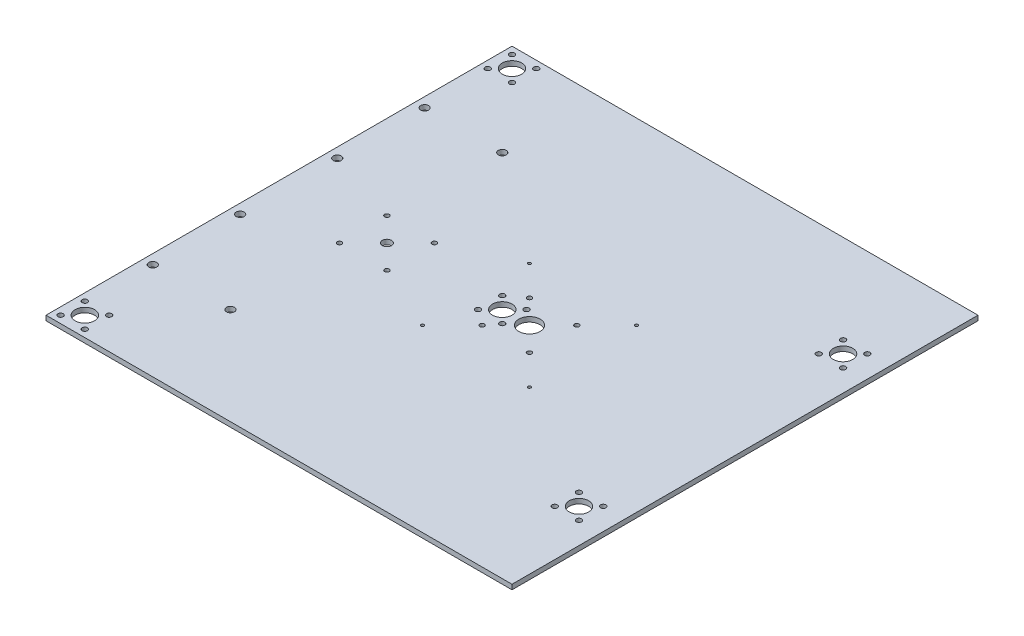
SolidWorks part; units mm, degrees
ref_plane "Front Plane" through (0, 0, 0) normal (0, 0, 1) x (1, 0, 0)
ref_plane "Top Plane" through (0, 0, 0) normal (0, 1, 0) x (1, 0, 0)
ref_plane "Right Plane" through (0, 0, 0) normal (1, 0, 0) x (0, 0, -1)
sketch "Sketch1" plane through (0, 0, 0) normal (0, 1, 0) x (1, 0, 0)
  line L1 (-152.4, -152.4) -> (152.4, -152.4)
  line L2 (-152.4, -152.4) -> (-152.4, 152.4)
  line L3 (-152.4, 152.4) -> (152.4, 152.4)
  line L4 (152.4, -152.4) -> (152.4, 152.4)
  line L5 (-152.4, -152.4) -> (152.4, 152.4) construction
  line L6 (-152.4, 152.4) -> (152.4, -152.4) construction
  point P0 (0, 0)
  dimension "D1" = 304.8
  dimension "D2" = 304.8
extrude "Boss-Extrude1" add sketch "Sketch1" along normal blind 3.175
sketch "Sketch2" plane through (0, 0, 0) normal (0, 1, 0) x (1, 0, 0)
  line L0 (-193.2668, 0) -> (192.9727, 0) construction
sketch "Sketch3" plane through (0, 3.175, 0) normal (0, 1, 0) x (1, 0, 0)
  circle A1 centre (-146.05, -31.75) radius 2.6
  circle A2 centre (-146.05, -31.75) radius 2.6
  circle A3 centre (-95.25, -88.9) radius 2.6
  circle A4 centre (-95.25, -88.9) radius 2.6
  circle A5 centre (-146.05, -88.9) radius 2.6
  circle A6 centre (-146.05, -88.9) radius 2.6
  dimension "D1" = 0
  dimension "D2" = 0
  dimension "D3" = 0
sketch "Sketch5" plane through (0, 3.175, 0) normal (0, 1, 0) x (1, 0, 0)
  circle A0 centre (-66.312, 15.5) radius 1.5 construction
  circle A1 centre (-66.312, -15.5) radius 1.5 construction
  circle A2 centre (-97.312, 15.5) radius 1.5 construction
  circle A3 centre (-97.312, -15.5) radius 1.5 construction
  circle A4 centre (-81.812, 0) radius 2.5 construction
  circle A5 centre (-66.312, 15.5) radius 1.5
  circle A6 centre (-66.312, -15.5) radius 1.5
  circle A7 centre (-97.312, 15.5) radius 1.5
  circle A8 centre (-97.312, -15.5) radius 1.5
  circle A9 centre (-81.812, 0) radius 2.5 construction
  circle A10 centre (-81.812, 0) radius 3
  dimension "D1" = 6
sketch "Sketch7" plane through (0, 3.175, 0) normal (0, 1, 0) x (1, 0, 0)
  circle A0 centre (46.4318, -35.0018) radius 1 construction
  circle A1 centre (-23.5718, -35.0018) radius 1 construction
  circle A2 centre (46.4318, -35.0018) radius 1
  circle A3 centre (-23.5718, -35.0018) radius 1
  circle A4 centre (-23.5718, 35.0018) radius 1 construction
  circle A5 centre (46.4318, 35.0018) radius 1 construction
  circle A6 centre (-23.5718, 35.0018) radius 1
  circle A7 centre (46.4318, 35.0018) radius 1
extrude "Cut-Extrude1" cut sketch "Sketch3" against normal through all
mirror "Mirror1" about plane through (0, 0, 0) normal (0, 0, 1) of "Cut-Extrude1"
extrude "Cut-Extrude2" cut sketch "Sketch5" against normal through all
extrude "Cut-Extrude3" cut sketch "Sketch7" against normal through all
sketch "Sketch9" plane through (0, 3.175, 0) normal (0, 1, 0) x (1, 0, 0)
  circle A0 centre (-131.7625, -147.6375) radius 1.727 construction
  circle A1 centre (-131.7625, -131.7625) radius 1.727 construction
  circle A2 centre (-147.6375, -131.7625) radius 1.727 construction
  circle A3 centre (-147.6375, -147.6375) radius 1.727 construction
  circle A4 centre (-139.7, -139.7) radius 6.35 construction
  circle A5 centre (-131.7625, -147.6375) radius 1.727
  circle A6 centre (-131.7625, -131.7625) radius 1.727
  circle A7 centre (-147.6375, -131.7625) radius 1.727
  circle A8 centre (-147.6375, -147.6375) radius 1.727
  circle A9 centre (-139.7, -139.7) radius 6.35
  circle A10 centre (138.1125, -94.2975) radius 1.727 construction
  circle A11 centre (138.1125, -78.4225) radius 1.727 construction
  circle A12 centre (130.175, -86.36) radius 6.35 construction
  circle A13 centre (122.2375, -78.4225) radius 1.727 construction
  circle A14 centre (122.2375, -94.2975) radius 1.727 construction
  circle A15 centre (138.1125, -94.2975) radius 1.727
  circle A16 centre (138.1125, -78.4225) radius 1.727
  circle A17 centre (130.175, -86.36) radius 6.35
  circle A18 centre (122.2375, -78.4225) radius 1.727
  circle A19 centre (122.2375, -94.2975) radius 1.727
  circle A20 centre (1.5875, 7.9375) radius 1.727 construction
  circle A21 centre (1.5875, -7.9375) radius 1.727 construction
  circle A22 centre (-6.35, 0) radius 6.35 construction
  circle A23 centre (-14.2875, -7.9375) radius 1.727 construction
  circle A24 centre (-14.2875, 7.9375) radius 1.727 construction
  circle A25 centre (1.5875, 7.9375) radius 1.727
  circle A26 centre (1.5875, -7.9375) radius 1.727
  circle A27 centre (-6.35, 0) radius 6.35
  circle A28 centre (-14.2875, -7.9375) radius 1.727
  circle A29 centre (-14.2875, 7.9375) radius 1.727
  circle A30 centre (122.2375, 94.2975) radius 1.727 construction
  circle A31 centre (122.2375, 78.4225) radius 1.727 construction
  circle A32 centre (138.1125, 94.2975) radius 1.727 construction
  circle A33 centre (130.175, 86.36) radius 6.35 construction
  circle A34 centre (138.1125, 78.4225) radius 1.727 construction
  circle A35 centre (122.2375, 94.2975) radius 1.727
  circle A36 centre (122.2375, 78.4225) radius 1.727
  circle A37 centre (138.1125, 94.2975) radius 1.727
  circle A38 centre (130.175, 86.36) radius 6.35
  circle A39 centre (138.1125, 78.4225) radius 1.727
  circle A40 centre (-131.7625, 131.7625) radius 1.727 construction
  circle A41 centre (-131.7625, 147.6375) radius 1.727 construction
  circle A42 centre (-147.6375, 147.6375) radius 1.727 construction
  circle A43 centre (-147.6375, 131.7625) radius 1.727 construction
  circle A44 centre (-131.7625, 131.7625) radius 1.727
  circle A45 centre (-131.7625, 147.6375) radius 1.727
  circle A46 centre (-147.6375, 147.6375) radius 1.727
  circle A47 centre (-147.6375, 131.7625) radius 1.727
  circle A48 centre (-139.7, 139.7) radius 6.35 construction
  circle A49 centre (-139.7, 139.7) radius 6.35
extrude "Cut-Extrude5" cut sketch "Sketch9" against normal through all both and the other way through all
sketch "Sketch11" plane through (0, 3.175, 0) normal (0, 1, 0) x (1, 0, 0)
  circle A0 centre (26.93, 15.5) radius 1.5 construction
  circle A1 centre (26.93, -15.5) radius 1.5 construction
  circle A2 centre (-4.07, -15.5) radius 1.5 construction
  circle A3 centre (-4.07, 15.5) radius 1.5 construction
  circle A4 centre (11.43, 0) radius 5.25 construction
  circle A5 centre (26.93, 15.5) radius 1.5
  circle A6 centre (26.93, -15.5) radius 1.5
  circle A7 centre (-4.07, -15.5) radius 1.5
  circle A8 centre (-4.07, 15.5) radius 1.5
  circle A9 centre (11.43, 0) radius 5.25 construction
  circle A10 centre (11.43, 0) radius 6.985
  dimension "D1" = 13.97
extrude "Cut-Extrude6" cut sketch "Sketch11" against normal through all both and the other way through all
equation "\"tightTol\"= 0.005in"
equation "\"normTol\"= 0.01in"
equation "\"looseTol\"= 0.02in"
equation "\"D1@Sketch5\"=6mm"
